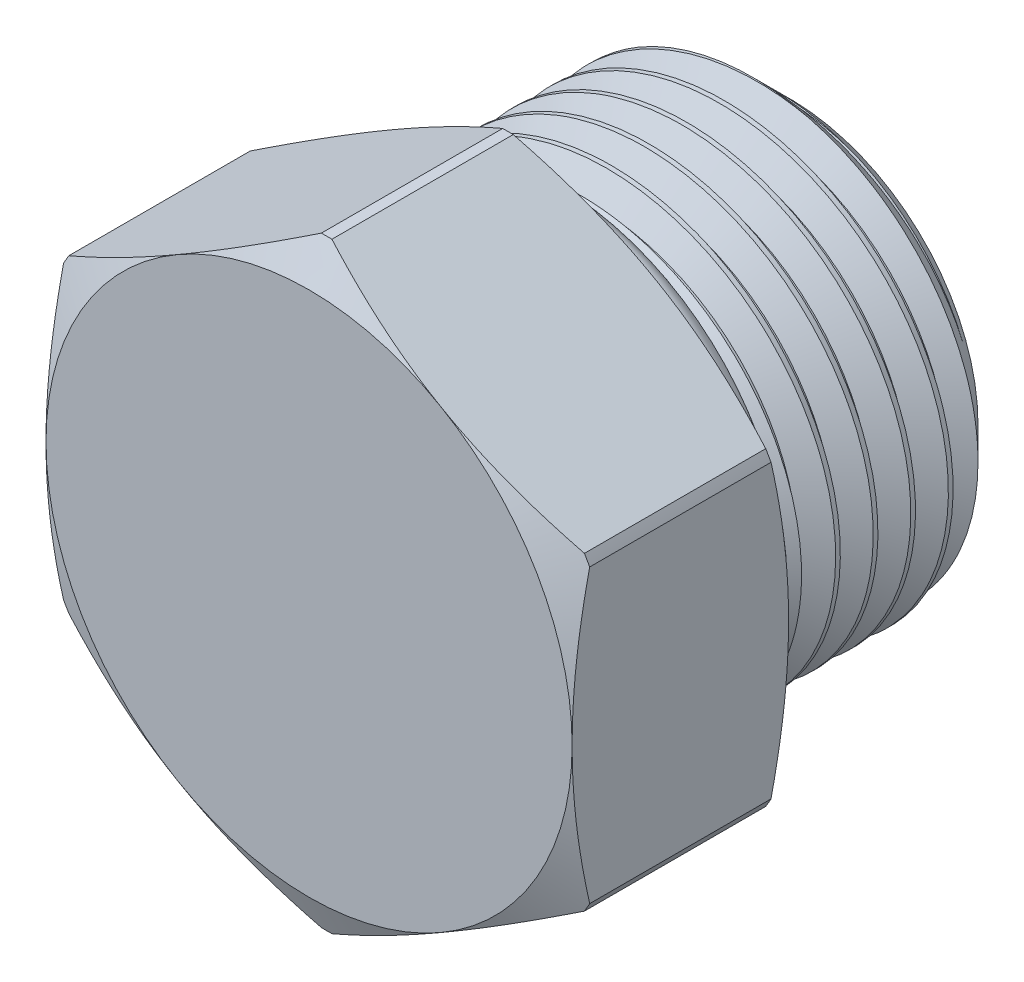
SolidWorks part; units mm, degrees
ref_plane "Front" through (0, 0, 0) normal (0, 0, 1) x (1, 0, 0)
ref_plane "Top" through (0, 0, 0) normal (0, 1, 0) x (1, 0, 0)
ref_plane "Right" through (0, 0, 0) normal (1, 0, 0) x (0, 0, -1)
ref_plane "Plane1" through (0, 0, -11.176) normal (0, 0, 1) x (1, 0, 0)
ref_plane "Plane2" through (0, 0, 9.144) normal (0, 0, 1) x (1, 0, 0)
sketch "Sketch1" plane through (0, 0, 0) normal (0, 0, 1) x (1, 0, 0)
  circle A0 centre (0, 0) radius 9.525
  dimension "OD" = 19.05
extrude "Extrude1" add sketch "Sketch1" against normal up to surface (11.176 mm away) up to plane "Plane1"
sketch "Sketch2" plane through (0, 0, 0) normal (0, 0, 1) x (1, 0, 0)
  circle A0 centre (0, 0) radius 9.525 construction
  circle A1 centre (0, 0) radius 9.525
chamfer "Chamfer1" distance 1.5875 angle 45 1 edges at (9.525, 0, -11.176)
curve "Helix/Spiral1" pitch 1.5875 height 14.351 radius 9.525 centre (0, 0, 0) axis (0, 0, -1) start towards (1, 0, 0) parameters "Lenght"=14.351, "Pitch"=1.5875
sketch "Sketch3" plane through (0, 0, 0) normal (1, 0, 0) x (0, 0, -1)
  line L1 (-1.3891, 9.525) -> (-0.7937, 8.4939)
  line L2 (-0.7937, 8.4939) -> (-0.5953, 8.4939)
  line L3 (-0.5953, 8.4939) -> (0, 9.525)
  line L6 (-1.3891, 9.525) -> (0, 9.525)
  line L7 (-0.6945, 9.525) -> (-0.6945, 8.4939) construction
  line L8 (-1.0914, 9.0094) -> (-0.2977, 9.0094) construction
  dimension "D1" = 0.1984
  dimension "D2" = 0.7937
  dimension "D4" = 60
sketch "Sketch11" plane through (0, 0, 0) normal (1, 0, 0) x (0, 0, -1)
  line L0 (0, 0) -> (11.176, 0) construction
  line L1 (11.176, -7.9375) -> (11.176, 7.9375) construction
  line L2 (0, 8.3344) -> (0, 9.525)
  line L3 (0, 8.7313) -> (0, -8.7313) construction
  line L4 (9.5885, 9.525) -> (0, 9.525) construction
  line L5 (0, 9.525) -> (2.3812, 9.525)
  line L6 (2.3812, 9.525) -> (1.1906, 8.3344)
  line L7 (1.1906, 8.3344) -> (0, 8.3344)
  dimension "D1" = 1.1906
  dimension "D2" = 45
revolve "Cut-Revolve2" cut sketch "Sketch11" angle 360 about L0
sweep "Cut-Sweep1" cut profiles "Sketch3" path "Helix/Spiral1" align with end faces yes
sketch "Sketch4" plane through (0, 0, 9.144) normal (0, 0, 1) x (1, 0, 0)
  circle A2 centre (0, 0) radius 8.4939
extrude "Extrude2" add sketch "Sketch4" against normal up to surface (9.144 mm away) up to face at (8.3344, 0, 0)
sketch "Sketch5" plane through (0, 0, 9.144) normal (0, 0, 1) x (1, 0, 0)
  line L1 (0, 12.8316) -> (-11.1125, 6.4158)
  line L2 (-11.1125, 6.4158) -> (-11.1125, -6.4158)
  line L3 (-11.1125, -6.4158) -> (0, -12.8316)
  line L4 (0, -12.8316) -> (11.1125, -6.4158)
  line L5 (11.1125, -6.4158) -> (11.1125, 6.4158)
  line L6 (11.1125, 6.4158) -> (0, 12.8316)
  circle A0 centre (0, 0) radius 11.1125 construction
  dimension "Hex" = 22.225
extrude "Extrude3" add sketch "Sketch5" against normal up to surface (9.144 mm away) up to plane "Front"
sketch "Sketch6" plane through (0, 0, 0) normal (1, 0, 0) x (0, 0, -1)
  line L0 (-9.144, 12.8316) -> (-9.144, 11.1125)
  line L1 (-9.144, 6.4158) -> (-9.144, 12.8316) construction
  line L2 (-9.144, 11.1125) -> (-8.4016, 12.7046)
  line L3 (-8.4016, 12.7046) -> (-0.7424, 12.7046)
  line L4 (-0.7424, 12.7046) -> (0, 11.1125)
  line L5 (0, 6.4158) -> (0, 12.8316) construction
  line L6 (0, 11.1125) -> (0, 12.8316)
  line L7 (0, 12.8316) -> (-9.144, 12.8316)
  line L8 (-4.572, 12.7046) -> (-4.572, 12.8316) construction
  line L10 (0, 6.4158) -> (0, 12.8316) construction
  line L11 (0, 0) -> (-9.144, 0) construction
  line L13 (-9.144, -6.4158) -> (-9.144, 6.4158) construction
  dimension "D1" = 25
  dimension "D2" = 0.127
  dimension "D3" = 22.225
revolve "Cut-Revolve1" cut sketch "Sketch6" angle 360 about L11
hole_wizard "Hole1" positions "Sketch9" profile "Sketch8" hole size "7/32" standard "Ansi Inch"
sketch "Sketch9" plane through (0, 0, -11.176) normal (0, 0, -1) x (-1, 0, 0)
  point P0 (0, 0)
sketch "Sketch8" plane through (0, 0, -11.176) normal (1, 0, 0) x (0, 1, 0)
  line L0 (0, 0) -> (0, 13.9755)
  line L1 (0, 13.9755) -> (6.35, 10.16)
  line L2 (6.35, 10.16) -> (6.35, 0)
  line L5 (6.35, 0) -> (0, 0)
  line L10 (0, 13.9755) -> (-6.35, 10.16) construction
  line L11 (0, -6.35) -> (0, 107.95) construction
  dimension "Hole Dia." = 12.7
  dimension "Hole Depth" = 10.16
  dimension "Drill Angle" = 118
sketch "Sketch10" plane through (0, 0, 0) normal (1, 0, 0) x (0, 0, -1)
  line L0 (0, 0) -> (-10.2394, 0) construction
  line L2 (0, 9.6237) -> (0, 11.1125) construction
  line L3 (1.1906, 8.3344) -> (0, 8.3344) construction
  circle A0 centre (0.7937, 9.1281) radius 0.7937
  dimension "D1" = 1.5875
revolve "Revolve1" add sketch "Sketch10" angle 360 about L0
equation "\"Lenght@Helix/Spiral1\"=\"Thread Lenght@Plane1\"+\"Pitch@Helix/Spiral1\"*2"
equation "\"D1@Chamfer1\"=\"Pitch@Helix/Spiral1\""
equation "\"D1@Sketch3\"=\"Pitch@Helix/Spiral1\"*0.125"
equation "\"D2@Sketch3\"=\"Pitch@Helix/Spiral1\"*0.50"
equation "\"D1@Sketch11\"=\"D1@Chamfer1\"*0.75"
equation "\"D3@Sketch6\"=\"Hex@Sketch5\""
equation "\"D1@Sketch10\"=\"Pitch@Helix/Spiral1\""
